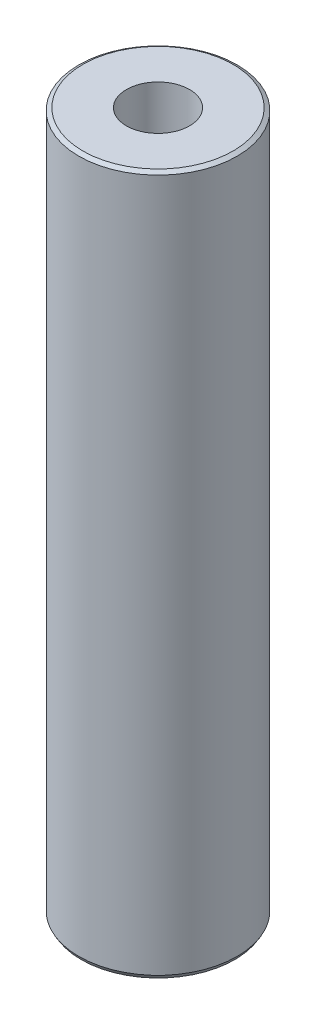
SolidWorks part; units mm, degrees
ref_plane "Front Plane" through (0, 0, 0) normal (0, 0, 1) x (1, 0, 0)
ref_plane "Top Plane" through (0, 0, 0) normal (0, 1, 0) x (1, 0, 0)
ref_plane "Right Plane" through (0, 0, 0) normal (1, 0, 0) x (0, 0, -1)
sketch "Sketch1" plane through (0, 0, 0) normal (0, 1, 0) x (1, 0, 0)
  circle A0 centre (0, 0) radius 27.5
  dimension "SHAFT_OD" = 55
extrude "Boss-Extrude1" add sketch "Sketch1" along normal blind 243.0201
sketch "Sketch2" plane through (0, 0, 0) normal (0, 1, 0) x (1, 0, 0)
  circle A0 centre (0, 0) radius 10.9569
  dimension "BORE_D" = 21.9139
extrude "Cut-Extrude1" cut sketch "Sketch2" along normal through all
chamfer "Chamfer1" distance 0.8509 angle 58.89 2 edges at (0, 243.0201, 27.5) (0, 0, 27.5) first distance on face at (0, 243.0201, 27.5) first distance on face at (0, 0, 10.9569)
